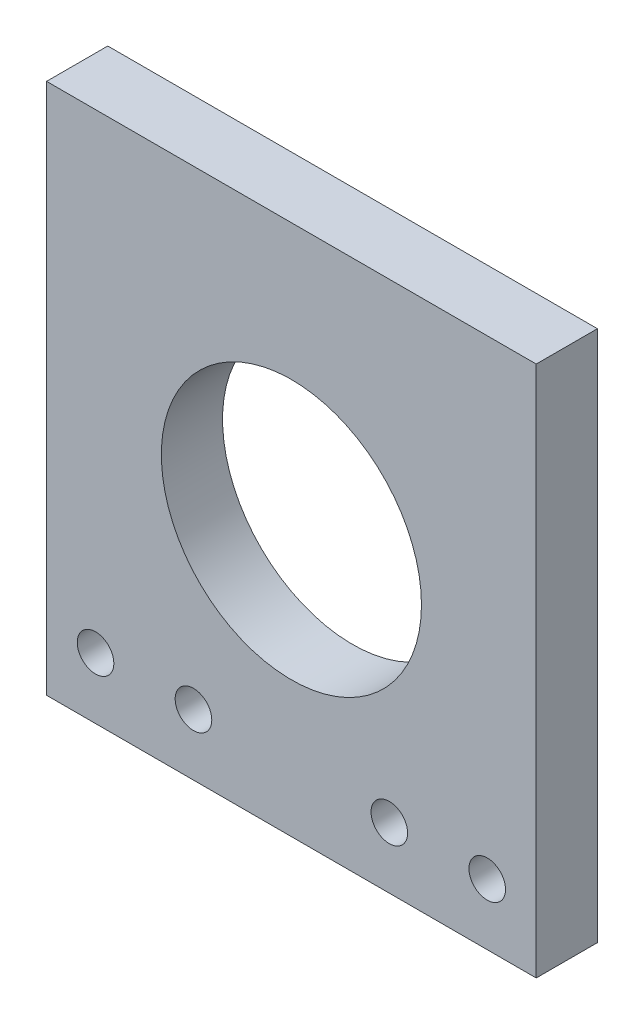
SolidWorks part; units mm, degrees
ref_plane "Front Plane" through (0, 0, 0) normal (0, 0, 1) x (1, 0, 0)
ref_plane "Top Plane" through (0, 0, 0) normal (0, 1, 0) x (1, 0, 0)
ref_plane "Right Plane" through (0, 0, 0) normal (1, 0, 0) x (0, 0, -1)
sketch "Sketch1" plane through (0, 0, 0) normal (0, 0, 1) x (1, 0, 0)
  line L1 (25.4, -27.5819) -> (-25.4, -27.5819)
  line L2 (25.4, -27.5819) -> (25.4, 27.5819)
  line L3 (25.4, 27.5819) -> (-25.4, 27.5819)
  line L4 (-25.4, -27.5819) -> (-25.4, 27.5819)
  line L5 (25.4, -27.5819) -> (-25.4, 27.5819) construction
  line L6 (25.4, 27.5819) -> (-25.4, -27.5819) construction
  circle A0 centre (0, 0) radius 13.4938
  point P0 (0, 0)
  dimension "D2" = 26.9875
  dimension "D1" = 50.8
  dimension "D3" = 55.1637
extrude "Boss-Extrude1" add sketch "Sketch1" along normal blind 6.35
hole_wizard "#6 Clearance Hole1" positions "Sketch2" profile "Sketch3" hole size "#6" standard "ANSI Inch" end condition through all
sketch "Sketch2" plane through (0, 0, 6.35) normal (0, 0, 1) x (1, 0, 0)
  line L0 (-20.32, -21.2319) -> (-10.16, -21.2319)
  line L2 (10.16, -21.2319) -> (20.32, -21.2319)
  line L4 (-25.4, -27.5819) -> (25.4, -27.5819) construction
  line L5 (-25.4, 27.5819) -> (-25.4, -27.5819) construction
  line L6 (25.4, -27.5819) -> (25.4, 27.5819) construction
  point P0 (-20.32, -21.2319)
  point P2 (-10.16, -21.2319)
  point P4 (10.16, -21.2319)
  point P6 (20.32, -21.2319)
  dimension "D1" = 10.16
  dimension "D2" = 10.16
  dimension "D3" = 6.35
  dimension "D4" = 6.35
  dimension "D5" = 5.08
  dimension "D6" = 5.08
sketch "Sketch3" plane through (-20.32, -21.2319, 6.35) normal (1, 0, 0) x (0, -1, 0)
  line L0 (0, 0) -> (0, 6.35)
  line L1 (0, 6.35) -> (1.8986, 6.35)
  line L2 (1.8986, 6.35) -> (1.8986, 0)
  line L5 (1.8986, 0) -> (0, 0)
  line L11 (0, -6.35) -> (0, 107.95) construction
  dimension "Thru Hole Dia." = 3.7973
  dimension "Thru Hole Depth" = 6.35
sketch "Sketch4" plane through (0, 0, 6.35) normal (0, 0, 1) x (1, 0, 0)
  line L0 (-25.4, 10.6598) -> (-8.478, 27.5819)
  line L1 (-25.4, 27.5819) -> (-25.4, -27.5819) construction
  line L2 (25.4, 27.5819) -> (-25.4, 27.5819) construction
  line L5 (-25.4, 10.6598) -> (-25.4, 27.5819)
  line L6 (-25.4, 27.5819) -> (-8.478, 27.5819)
